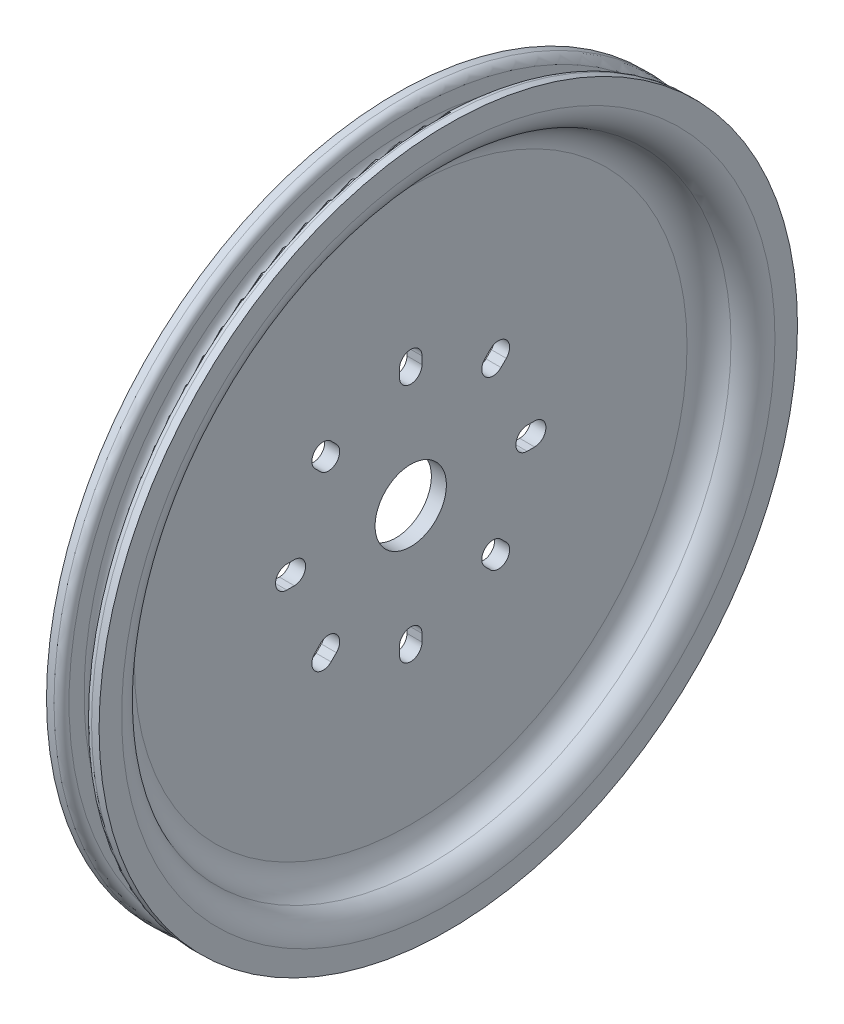
SolidWorks part; units mm, degrees
material "ABS"
ref_plane "Plan de face" through (0, 0, 0) normal (0, 0, 1) x (1, 0, 0)
ref_plane "Plan de dessus" through (0, 0, 0) normal (0, 1, 0) x (1, 0, 0)
ref_plane "Plan de droite" through (0, 0, 0) normal (1, 0, 0) x (0, 0, -1)
sketch "Esquisse1" plane through (0, 0, 0) normal (0, 0, 1) x (1, 0, 0)
  line L0 (1, 0) -> (-1, 0) construction
  line L1 (-1, 46.5) -> (1, 46.5)
  line L2 (-1, 46.5) -> (-1, 4.75)
  line L4 (1, 36.7918) -> (1, 4.75)
  line L5 (1, 46.5) -> (1, 43.5)
  line L6 (4, 43.5) -> (4, 46.5)
  line L7 (4, 46.5) -> (6, 46.5)
  line L8 (6, 46.5) -> (6, 43.5)
  line L9 (-1, 4.75) -> (1, 4.75)
  arc A0 (1, 43.5) -> (4, 43.5) centre (2.5, 43.5) ccw
  arc A1 (6, 43.5) -> (3.5, 40.1459) centre (2.5, 43.5) cw
  arc A2 (3.5, 40.1459) -> (1, 36.7918) centre (4.5, 36.7918) ccw
  point P3 (2.5, 42)
  dimension "D1" = 3
  dimension "D5" = 84
  dimension "D2" = 2
  dimension "D3" = 2
  dimension "D4" = 3
  dimension "D6" = 9.5
  dimension "D7" = 93
revolve "Révolution1" add sketch "Esquisse1" angle 360 about L0
fillet "Congé1" radius 1 2 edges at (4, 0, -46.5) (1, 0, -46.5)
sketch "Esquisse2" plane through (0, 0, 0) normal (0, 1, 0) x (1, 0, 0)
  line L0 (-1, 0) -> (6, 0) construction
  line L1 (-1, 46.5) -> (-1, -46.5) construction
  line L2 (6, -43.5) -> (6, 43.5) construction
  circle A0 centre (2.5, 2.5) radius 1.25
  circle A1 centre (2.5, -2.5) radius 1.25
  point P8 (2.5, 0)
  dimension "D1" = 5
  dimension "D2" = 2.5
extrude "Enlèv. mat.-Extru.1" cut sketch "Esquisse2" along normal through all from offset 35
fillet "Congé2" radius 1 2 edges at (3.0505, 42.0821, -1.3777) (3.02, 41.9356, 3.6367)
sketch "Esquisse3" plane through (-1, 0, 0) normal (-1, 0, 0) x (0, 0, 1)
  line L0 (0, 16.5) -> (0, 15.5) construction
  line L1 (1.5, 16.5) -> (1.5, 15.5)
  line L2 (-1.5, 16.5) -> (-1.5, 15.5)
  arc A0 (1.5, 16.5) -> (-1.5, 16.5) centre (0, 16.5) ccw
  arc A1 (-1.5, 15.5) -> (1.5, 15.5) centre (0, 15.5) ccw
  point P3 (0, 16)
  dimension "D1" = 16
  dimension "D2" = 1
  dimension "D3" = 3
extrude "Enlèv. mat.-Extru.2" cut sketch "Esquisse3" against normal through all
pattern_circular "Répétition circulaire1" count 8 over 360 about axis through (-1, 0, 0) along (1, 0, 0) of "Enlèv. mat.-Extru.2"
